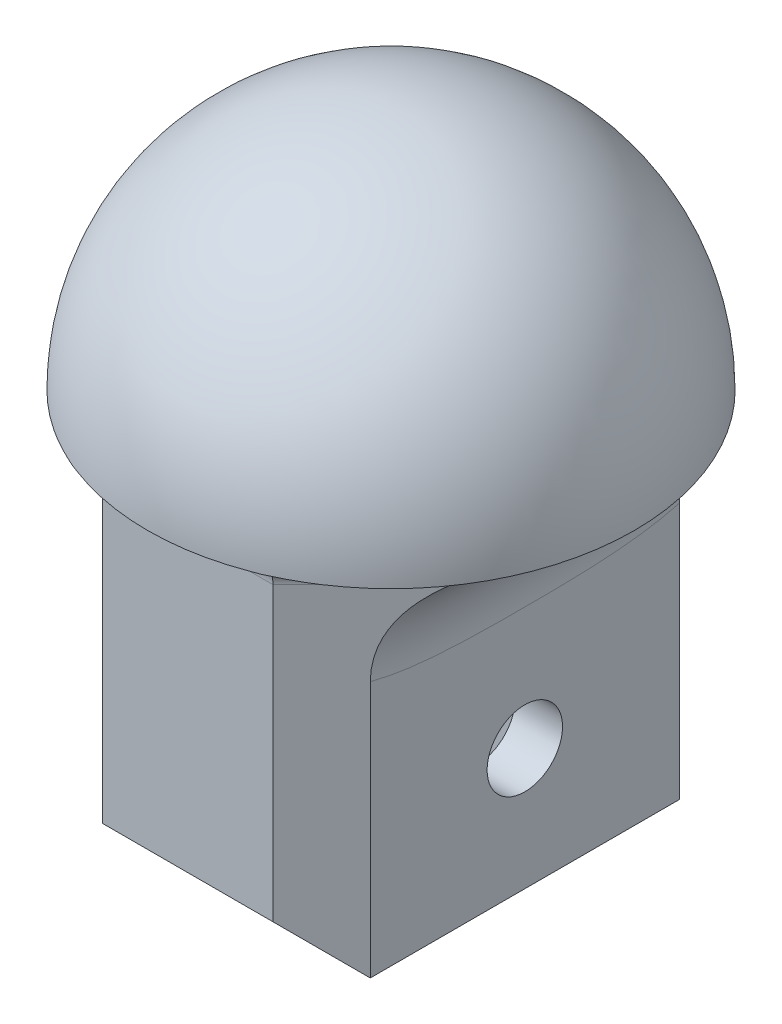
SolidWorks part; units mm, degrees
material "天然橡胶"
ref_plane "前视基准面" through (0, 0, 0) normal (0, 0, 1) x (1, 0, 0)
ref_plane "上视基准面" through (0, 0, 0) normal (0, 1, 0) x (1, 0, 0)
ref_plane "右视基准面" through (0, 0, 0) normal (1, 0, 0) x (0, 0, -1)
other "Configuration Table"
sketch "草图1" plane through (0, 0, 0) normal (0, 0, 1) x (1, 0, 0)
  line L1 (0, 0) -> (0, 10) construction
  line L3 (0, 0) -> (10, 0)
  line L4 (0, 0) -> (0, 10)
  arc A1 (10, 0) -> (0, 10) centre (0, 0) ccw
  dimension "D2" = 90
  dimension "D1" = 10
  dimension "D3" = 10
revolve "旋转2" add sketch "草图1" angle 360 about L1
sketch "草图2" plane through (0, 0, 0) normal (0, -1, 0) x (1, 0, 0)
  line L1 (-5.5, 8.3516) -> (5.5, 8.3516)
  line L2 (-5.5, 8.3516) -> (-5.5, -8.3516)
  line L3 (-5.5, -8.3516) -> (5.5, -8.3516)
  line L4 (5.5, 8.3516) -> (5.5, -8.3516)
  line L5 (0, -8.3516) -> (0, 8.3516) construction
  line L6 (-5.5, 0) -> (5.5, 0) construction
  circle A0 centre (0, 0) radius 10 construction
  point P0 (0, 0)
  dimension "D1" = 11
extrude "凸台-拉伸1" add sketch "草图2" along normal blind 15
sketch "草图3" plane through (0, -15, 0) normal (0, -1, 0) x (1, 0, 0)
  line L1 (-3.55, 4) -> (3.55, 4)
  line L2 (-3.55, 4) -> (-3.55, -4)
  line L3 (-3.55, -4) -> (3.55, -4)
  line L4 (3.55, 4) -> (3.55, -4)
  line L5 (0, -4) -> (0, 4) construction
  line L6 (-3.55, 0) -> (3.55, 0) construction
  point P0 (0, 0)
  dimension "D1" = 8
  dimension "D2" = 7.1
extrude "切除-拉伸1" cut sketch "草图3" against normal blind 15
sketch "草图4" plane through (-5.5, 0, 0) normal (-1, 0, 0) x (0, 0, 1)
  line L0 (0, -15) -> (0, -10) construction
  line L1 (8.3516, -15) -> (-8.3516, -15) construction
  circle A0 centre (0, -10) radius 1.55
  dimension "D2" = 3.1
  dimension "D1" = 5
extrude "切除-拉伸2" cut sketch "草图4" against normal through all
chamfer "倒角1" distance 2 angle 45 6 edges at (0, -15, -8.3516) (0, -15, 8.3516) (5.5, -7.5, 8.3516) (-5.5, -7.5, 8.3516) (-5.5, -7.5, -8.3516) (5.5, -7.5, -8.3516)
fillet "圆角1" radius 5 2 edges at (5.5, 0, 0) (-5.5, 0, 0)
fillet "圆角2" radius 1 6 edges at (-6.6419, 0, 5.2097) (6.6419, 0, 5.2097) (0, 0, 8.3516) (6.6419, 0, -5.2097) (-6.6419, 0, -5.2097) (0, 0, -8.3516)
